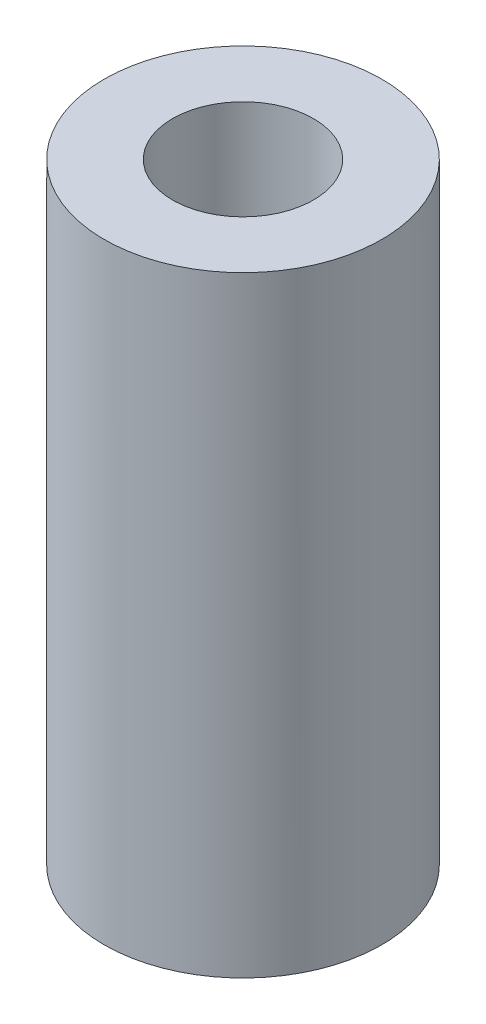
SolidWorks part; units mm, degrees
ref_plane "Front Plane" through (0, 0, 0) normal (0, 0, 1) x (1, 0, 0)
ref_plane "Top Plane" through (0, 0, 0) normal (0, 1, 0) x (1, 0, 0)
ref_plane "Right Plane" through (0, 0, 0) normal (1, 0, 0) x (0, 0, -1)
sketch "Sketch1" plane through (0, 0, 0) normal (0, 1, 0) x (1, 0, 0)
  circle A0 centre (0, 0) radius 6.35
  arc A4 (5.8189, -2.5423) -> (-4.3592, 4.6174) centre (0, 0) ccw construction
  circle A5 centre (0, 0) radius 3.2258
  circle A6 centre (0, 0) radius 3.2258
  dimension "D1" = 0.0508
extrude "Boss-Extrude1" add sketch "Sketch1" along normal up to surface (27.9373 mm away)
